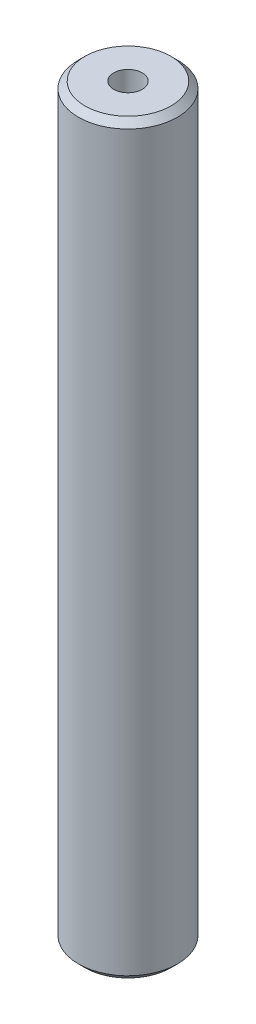
SolidWorks part; units mm, degrees
ref_plane "Front Plane" through (0, 0, 0) normal (0, 0, 1) x (1, 0, 0)
ref_plane "Top Plane" through (0, 0, 0) normal (0, 1, 0) x (1, 0, 0)
ref_plane "Right Plane" through (0, 0, 0) normal (1, 0, 0) x (0, 0, -1)
sketch "Sketch1" plane through (0, 0, 0) normal (0, 1, 0) x (1, 0, 0)
  circle A0 centre (0, 0) radius 30
  dimension "SHAFT_OD" = 60
extrude "Boss-Extrude1" add sketch "Sketch1" along normal blind 452.0856
sketch "Sketch2" plane through (0, 0, 0) normal (0, 1, 0) x (1, 0, 0)
  circle A0 centre (0, 0) radius 8.6667
  dimension "BORE_D" = 17.3334
extrude "Cut-Extrude1" cut sketch "Sketch2" along normal through all
chamfer "Chamfer1" distance 3.9494 angle 45 2 edges at (0, 452.0856, 30) (0, 0, 30)
